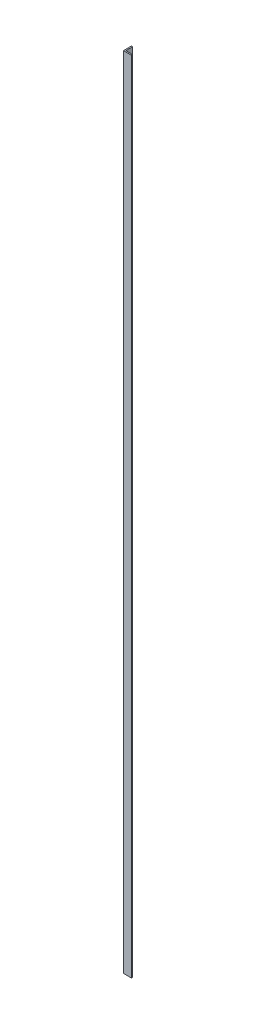
SolidWorks part; units mm, degrees
ref_plane "Front Plane" through (0, 0, 0) normal (0, 0, 1) x (1, 0, 0)
ref_plane "Top Plane" through (0, 0, 0) normal (0, 1, 0) x (1, 0, 0)
ref_plane "Right Plane" through (0, 0, 0) normal (1, 0, 0) x (0, 0, -1)
sketch "Sketch1" plane through (0, 0, 0) normal (0, 1, 0) x (1, 0, 0)
  line L2 (0, 0) -> (0, 50.8)
  line L3 (0, 50.8) -> (7.62, 50.8)
  line L4 (7.62, 7.62) -> (7.62, 50.8)
  line L5 (0, 0) -> (50.8, 0)
  line L7 (7.62, 7.62) -> (50.8, 7.62)
  line L8 (50.8, 0) -> (50.8, 7.62)
  dimension "D1" = 50.8
  dimension "D2" = 7.62
  dimension "D3" = 50.8
  dimension "D4" = 7.62
extrude "Boss-Extrude1" add sketch "Sketch1" along normal blind 5080
equation "\"in\"=1.0212"
